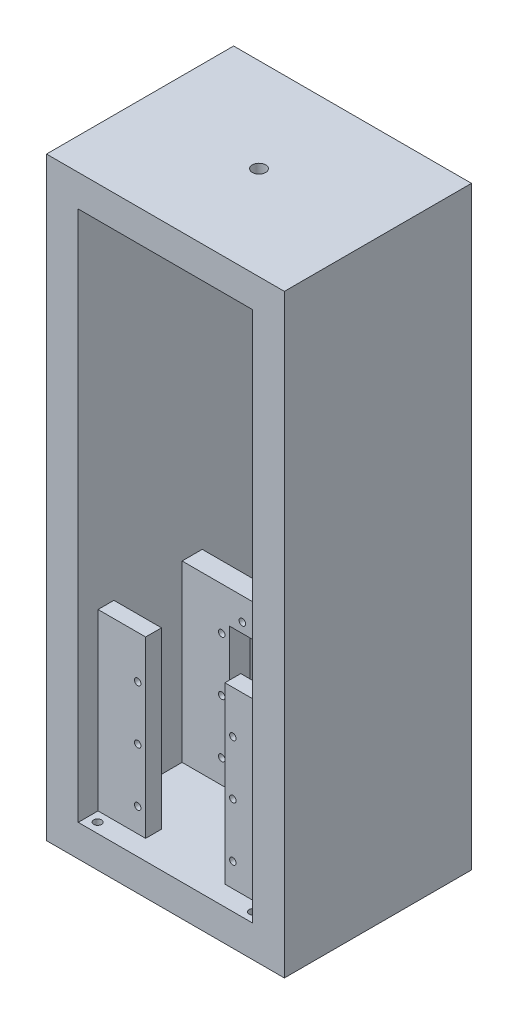
SolidWorks part; units mm, degrees
material "6061 Alloy"
ref_plane "Front Plane" through (0, 0, 0) normal (0, 0, 1) x (1, 0, 0)
ref_plane "Top Plane" through (0, 0, 0) normal (0, 1, 0) x (1, 0, 0)
ref_plane "Right Plane" through (0, 0, 0) normal (1, 0, 0) x (0, 0, -1)
sketch "Sketch1" plane through (0, 0, 0) normal (0, 0, 1) x (1, 0, 0)
  line L1 (0, 0) -> (75, 0)
  line L2 (0, 0) -> (0, 187.5)
  line L3 (0, 187.5) -> (75, 187.5)
  line L4 (75, 0) -> (75, 187.5)
  line L5 (10, 10) -> (65, 10)
  line L6 (10, 10) -> (10, 177.5)
  line L7 (10, 177.5) -> (65, 177.5)
  line L8 (65, 10) -> (65, 177.5)
  dimension "D1" = 75
  dimension "D2" = 187.5
  dimension "D3" = 10
  dimension "D4" = 10
  dimension "D5" = 10
  dimension "D6" = 10
extrude "Boss-Extrude1" add sketch "Sketch1" against normal blind 59
ref_plane "Plane1" through (0, 0, -37.5) normal (0, 0, 1) x (1, 0, 0)
hole_wizard "Tap Drill for M5x0.8 Tap2" positions "Sketch8" profile "Sketch9" hole size "M5x0.8" standard "ANSI Metric" end condition through all
sketch "Sketch8" plane through (0, 10, 0) normal (0, 1, 0) x (1, 0, 0)
  line L0 (37.5, 59) -> (37.5, 0) construction
  line L1 (10, 59) -> (65, 59) construction
  line L2 (10, 0) -> (65, 0) construction
  point P0 (37.5, 29.5)
sketch "Sketch9" plane through (37.5, 10, -29.5) normal (1, 0, 0) x (0, 0, 1)
  line L0 (0, 0) -> (0, 10)
  line L1 (0, 10) -> (2.1, 10)
  line L2 (2.1, 10) -> (2.1, 0)
  line L5 (2.1, 0) -> (0, 0)
  line L11 (0, -6.35) -> (0, 107.95) construction
  dimension "Thru Hole Dia." = 4.2
  dimension "Thru Hole Depth" = 10
hole_wizard "Tap Drill for M5x0.8 Tap3" positions "Sketch11" profile "Sketch12" hole size "M5x0.8" standard "ANSI Metric"
sketch "Sketch11" plane through (0, 187.5, 0) normal (0, 1, 0) x (1, 0, 0)
  line L0 (0, 29.5) -> (75, 29.5) construction
  line L1 (0, 59) -> (0, 0) construction
  line L2 (75, 59) -> (75, 0) construction
  point P0 (37.5, 29.5)
sketch "Sketch12" plane through (37.5, 187.5, -29.5) normal (1, 0, 0) x (0, 0, 1)
  line L0 (0, 0) -> (0, 11.2618)
  line L1 (0, 11.2618) -> (2.1, 10)
  line L2 (2.1, 10) -> (2.1, 0)
  line L5 (2.1, 0) -> (0, 0)
  line L10 (0, 11.2618) -> (-2.1, 10) construction
  line L11 (0, -6.35) -> (0, 107.95) construction
  dimension "Hole Dia." = 4.2
  dimension "Hole Depth" = 10
  dimension "Drill Angle" = 118
sketch "Sketch13" plane through (0, 10, 0) normal (0, 1, 0) x (1, 0, 0)
  line L0 (65, 59) -> (65, 0) construction
  line L1 (65, 32.75) -> (50, 32.75)
  line L2 (65, 32.75) -> (65, 39.1)
  line L3 (65, 39.1) -> (50, 39.1)
  line L4 (50, 32.75) -> (50, 39.1)
  line L5 (37.5, 59) -> (37.5, 0) construction
  line L6 (10, 59) -> (65, 59) construction
  line L7 (10, 0) -> (65, 0) construction
  line L8 (10, 39.1) -> (25, 39.1)
  line L9 (25, 32.75) -> (25, 39.1)
  line L10 (10, 32.75) -> (25, 32.75)
  line L11 (10, 32.75) -> (10, 39.1)
  line L12 (10, 11.25) -> (25, 11.25)
  line L13 (65, 6.25) -> (50, 6.25)
  line L14 (65, 6.25) -> (65, 11.25)
  line L15 (65, 11.25) -> (50, 11.25)
  line L16 (50, 6.25) -> (50, 11.25)
  line L17 (25, 6.25) -> (25, 11.25)
  line L18 (10, 6.25) -> (25, 6.25)
  line L19 (10, 6.25) -> (10, 11.25)
  dimension "D1" = 26.25
  dimension "D2" = 12.5
  dimension "D3" = 6.35
  dimension "D4" = 6.25
  dimension "D5" = 5
  dimension "D6" = 15
extrude "Boss-Extrude2" add sketch "Sketch13" along normal blind 55
sketch "Sketch14" plane through (50, 0, 0) normal (-1, 0, 0) x (0, 0, 1)
  line L0 (-32.75, 65) -> (-32.75, 10) construction
  line L1 (-39.1, 65) -> (-32.75, 65)
  line L2 (-39.1, 65) -> (-39.1, 54.7)
  line L3 (-39.1, 54.7) -> (-32.75, 54.7)
  line L4 (-32.75, 65) -> (-32.75, 54.7)
  dimension "D1" = 10.3
extrude "Boss-Extrude3" add sketch "Sketch14" along normal up to surface (25 mm away) contours L1 L4 L3 L2 up to face at (25, 37.5, -35.925)
sketch "Sketch17" plane through (0, 0, -39.1) normal (0, 0, -1) x (-1, 0, 0)
  line L0 (-37.5, 65) -> (-37.5, 10) construction
  line L1 (-65, 65) -> (-10, 65) construction
  line L2 (-10, 10) -> (-65, 10) construction
  line L3 (-22.5, 65) -> (-22.5, 10) construction
  line L5 (-25, 10) -> (-10, 10) construction
  line L6 (-29, 65) -> (-29, 10) construction
  line L8 (-65, 17.5) -> (-10, 17.5) construction
  line L9 (-65, 10) -> (-65, 177.5) construction
  line L10 (-10, 65) -> (-10, 10) construction
  line L11 (-65, 34.5) -> (-10, 34.5) construction
  line L12 (-65, 51.5) -> (-10, 51.5) construction
  line L13 (-65, 57.8) -> (-10, 57.8) construction
  line L14 (-52.5, 65) -> (-52.5, 10) construction
  line L15 (-46, 65) -> (-46, 10) construction
  dimension "D1" = 15
  dimension "D2" = 6.5
  dimension "D3" = 7.5
  dimension "D4" = 17
  dimension "D5" = 17
  dimension "D6" = 6.3
hole_wizard "Tap Drill for M2.5x0.45 Tap1" positions "Sketch18" profile "Sketch19" hole size "M2.5x0.45" standard "ANSI Metric" end condition through all
sketch "Sketch18" plane through (0, 0, -39.1) normal (0, 0, -1) x (-1, 0, 0)
  line L0 (-65, 57.8) -> (-10, 57.8) construction
  line L1 (-46, 65) -> (-46, 10) construction
  line L2 (-29, 65) -> (-29, 10) construction
  line L3 (-22.5, 65) -> (-22.5, 10) construction
  line L4 (-65, 51.5) -> (-10, 51.5) construction
  line L5 (-52.5, 65) -> (-52.5, 10) construction
  line L6 (-65, 34.5) -> (-10, 34.5) construction
  line L7 (-65, 17.5) -> (-10, 17.5) construction
  point P0 (-46, 57.8)
  point P2 (-52.5, 51.5)
  point P4 (-52.5, 34.5)
  point P6 (-52.5, 17.5)
  point P8 (-22.5, 17.5)
  point P10 (-22.5, 34.5)
  point P12 (-22.5, 51.5)
  point P14 (-29, 57.8)
sketch "Sketch19" plane through (46, 57.8, -39.1) normal (1, 0, 0) x (0, 1, 0)
  line L0 (0, 0) -> (0, 39.1)
  line L1 (0, 39.1) -> (1.025, 39.1)
  line L2 (1.025, 39.1) -> (1.025, 0)
  line L5 (1.025, 0) -> (0, 0)
  line L11 (0, -6.35) -> (0, 107.95) construction
  dimension "Thru Hole Dia." = 2.05
  dimension "Thru Hole Depth" = 39.1
hole_wizard "Tap Drill for M3x0.5 Tap1" positions "Sketch20" profile "Sketch21" hole size "M3x0.5" standard "ANSI Metric" end condition through all
sketch "Sketch20" plane through (0, 10, 0) normal (0, 1, 0) x (1, 0, 0)
  line L0 (10, 3.125) -> (65, 3.125) construction
  line L1 (10, 6.25) -> (10, 0) construction
  line L2 (65, 6.25) -> (65, 0) construction
  line L4 (13, 6.25) -> (13, 0) construction
  line L5 (10, 6.25) -> (25, 6.25) construction
  line L6 (10, 0) -> (65, 0) construction
  line L8 (62, 6.25) -> (62, 0) construction
  line L9 (50, 6.25) -> (65, 6.25) construction
  line L11 (65, 53) -> (10, 53)
  line L12 (65, 59) -> (65, 39.1) construction
  line L13 (10, 59) -> (10, 39.1) construction
  line L15 (10, 59) -> (65, 59) construction
  line L16 (60, 53) -> (60, 59) construction
  line L18 (15, 53) -> (15, 59) construction
  point P0 (13, 3.125)
  point P2 (62, 3.125)
  point P37 (60, 53)
  point P39 (15, 53)
  dimension "D1" = 3
  dimension "D2" = 3
  dimension "D3" = 6
  dimension "D4" = 5
  dimension "D5" = 5
sketch "Sketch21" plane through (13, 10, -3.125) normal (1, 0, 0) x (0, 0, 1)
  line L0 (0, 0) -> (0, 10)
  line L1 (0, 10) -> (1.25, 10)
  line L2 (1.25, 10) -> (1.25, 0)
  line L5 (1.25, 0) -> (0, 0)
  line L11 (0, -6.35) -> (0, 107.95) construction
  dimension "Thru Hole Dia." = 2.5
  dimension "Thru Hole Depth" = 10
